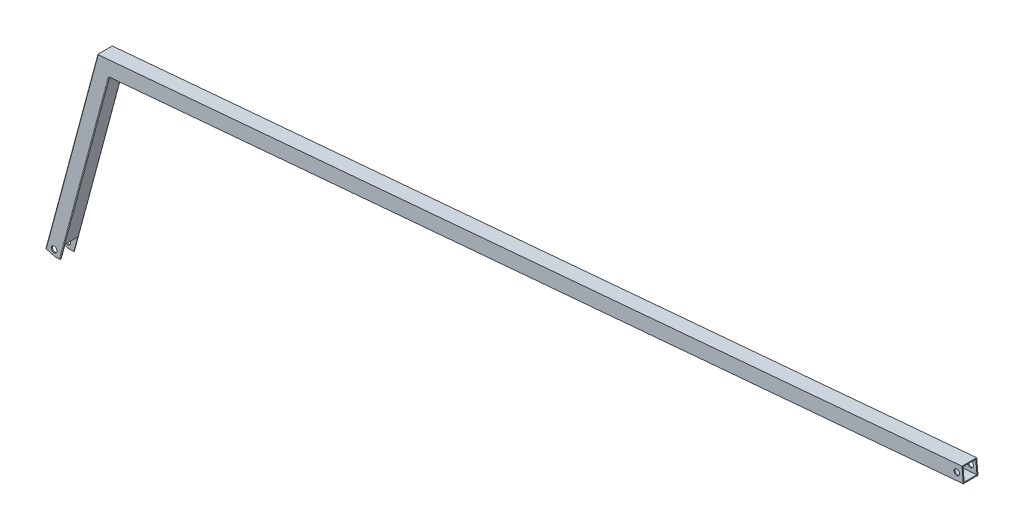
SolidWorks part; units mm, degrees
ref_plane "Front Plane" through (0, 0, 0) normal (0, 0, 1) x (1, 0, 0)
ref_plane "Top Plane" through (0, 0, 0) normal (0, 1, 0) x (1, 0, 0)
ref_plane "Right Plane" through (0, 0, 0) normal (1, 0, 0) x (0, 0, -1)
sketch "Sketch1" plane through (0, 0, 0) normal (0, 0, -1) x (-1, 0, 0)
  line L0 (32.8955, -12.8153) -> (1525.825, -143.4297)
  line L1 (1525.825, -143.4297) -> (1615.5675, -478.3534)
  line L2 (1615.5675, -478.3534) -> (1591.033, -484.9274)
  line L3 (1591.033, -484.9274) -> (1505.8936, -167.183)
  line L4 (1505.8936, -167.183) -> (30.6818, -38.1187)
  line L5 (30.6818, -38.1187) -> (32.8955, -12.8153)
  line L6 (22.8132, -24.6817) -> (105.6727, -31.931) construction
  line L7 (804.8625, -431.8) -> (1577.975, -431.8) construction
  line L8 (1577.975, -298.45) -> (1577.975, -431.8) construction
  line L9 (1592.5525, -441.5294) -> (-11348.3997, 47854.7619) construction
  circle A0 centre (41.91, -26.3525) radius 4.826
  circle A1 centre (41.91, -26.3525) radius 4.8641 construction
  circle A2 centre (1600.835, -472.44) radius 4.826
  circle A3 centre (1600.835, -472.44) radius 5.08 construction
  point P9 (31.7887, -25.467)
  point P15 (0, 0)
  point P18 (1537.3319, -407.9179)
  point P19 (0, 0)
  point P24 (1560.8115, -404.6935)
  point P25 (1502.0267, -416.8004)
  point P26 (1558.8677, -402.6313)
  point P27 (0, 0)
  dimension "D3" = 9.652
  dimension "D1" = 25.4
  dimension "D2" = 25.4
  dimension "D4" = 10.16
  dimension "D5" = 5
  dimension "D6" = 15
  dimension "D7" = 9.525
extrude "Boss-Extrude1" add sketch "Sketch1" along normal mid plane 25.4 contours A2 | A0 | L3 L4 L5 L0 L1 L2 region at (-41.91, -26.3525, 0) region at (-1600.835, -472.44, 0)
shell "Shell1" thickness 1.651 removed face at (-31.7887, -25.467, 0) removed face at (-1605.661, -472.44, -12.7) removed face at (-1603.3003, -481.6404, 0) removed face at (-46.736, -26.3525, -12.7)
fillet "Fillet1" radius 1.27 8 edges at (-1569.2511, -311.8772, -11.049) (-1569.2511, -311.8772, 11.049) (-1549.9084, -325.0696, -11.049) (-1549.9084, -325.0696, 11.049) (-1548.4633, -326.0552, 12.7) (-1570.6962, -310.8916, 12.7) (-1570.6962, -310.8916, -12.7) (-1548.4633, -326.0552, -12.7)
sketch "Sketch2" plane through (0, 0, -12.7) normal (0, 0, -1) x (-1, 0, 0)
  line L0 (1599.7191, -482.6) -> (1590.4094, -482.6)
  line L1 (1614.3408, -478.6821) -> (1592.2597, -484.5987) construction
  line L2 (-57.15, -482.6) -> (1616.075, -482.6) construction
  line L3 (1591.033, -484.9274) -> (1505.8936, -167.183) construction
  line L4 (1590.4094, -482.6) -> (1591.033, -484.9274)
  line L5 (1591.033, -484.9274) -> (1599.7191, -482.6)
extrude "Cut-Extrude1" cut sketch "Sketch2" against normal through all
sketch "Sketch3" plane through (0, 0, 0) normal (1, 0, 0) x (0, 0, -1)
  line L1 (11.049, -482.6) -> (-11.049, -482.6)
  line L2 (11.049, -482.6) -> (11.049, -457.2)
  line L3 (11.049, -457.2) -> (-11.049, -457.2)
  line L4 (-11.049, -482.6) -> (-11.049, -457.2)
  line L5 (-6.8834, -462.28) -> (6.8834, -462.28) construction
  line L6 (0, -1000) -> (0, 49000) construction
  line L7 (762, -482.6) -> (-1635.125, -482.6) construction
  line L10 (-11.049, -477.266) -> (-11.049, -467.614) construction
  dimension "D1" = 5.08
extrude "Cut-Extrude2" cut sketch "Sketch3" against normal through all
fillet "Fillet2" radius 1.27 4 edges at (-1608.3874, -457.2, -11.049) (-1585.1155, -457.2, -11.049) (-1608.3874, -457.2, 11.049) (-1585.1155, -457.2, 11.049)
